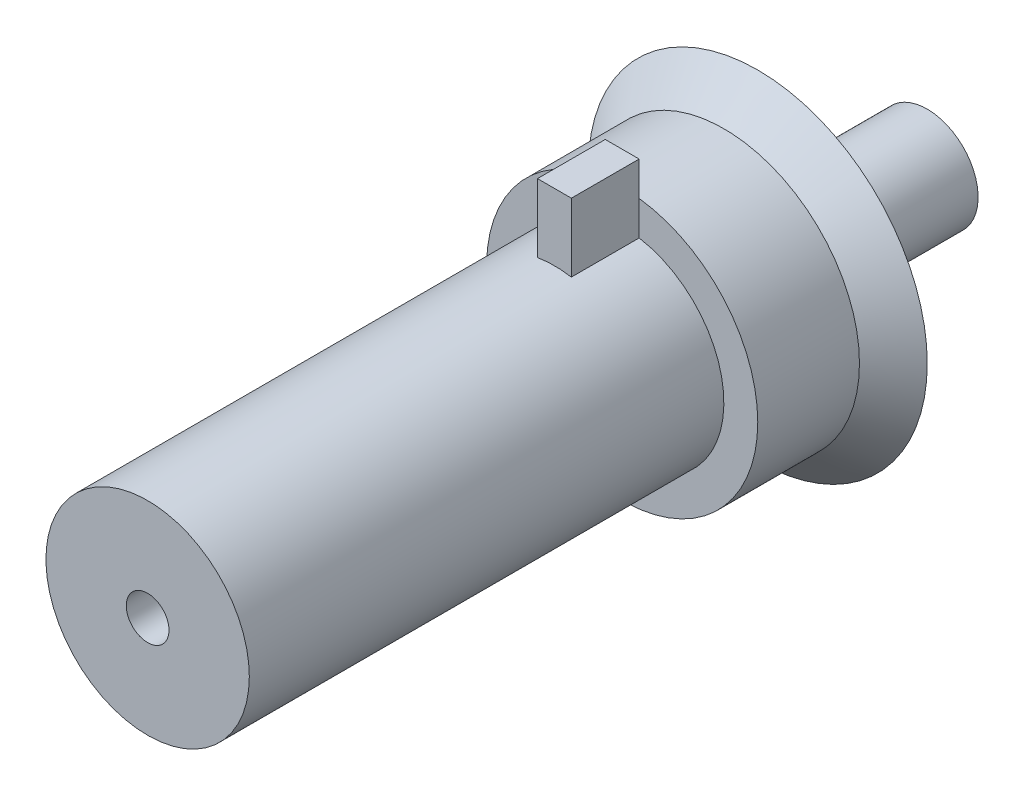
SolidWorks part; units mm, degrees
ref_plane "Front Plane" through (0, 0, 0) normal (0, 0, 1) x (1, 0, 0)
ref_plane "Top Plane" through (0, 0, 0) normal (0, 1, 0) x (1, 0, 0)
ref_plane "Right Plane" through (0, 0, 0) normal (1, 0, 0) x (0, 0, -1)
sketch "Sketch1" plane through (0, 0, 0) normal (0, 0, 1) x (1, 0, 0)
  circle A0 centre (0, 0) radius 15
  dimension "D1" = 30
extrude "Boss-Extrude1" add sketch "Sketch1" along normal blind 80
ref_plane "Plane1" through (0, 0, -10) normal (0, 0, -1) x (-1, 0, 0)
sketch "Sketch2" plane through (0, 0, -10) normal (0, 0, -1) x (-1, 0, 0)
  circle A0 centre (0, 0) radius 25
  dimension "D1" = 50
loft "Loft1" add profiles "Sketch1<2>", "Sketch2" connector at (1.8145, 14.8898, 0) connector at (2.7327, 24.8502, -10)
sketch "Sketch1<2>" plane through (0, 0, 0) normal (0, 0, 1) x (1, 0, 0) same geometry as "Sketch1"
sketch "Sketch3" plane through (0, 0, -10) normal (0, 0, -1) x (-1, 0, 0)
  circle A0 centre (0, 0) radius 7.5
  dimension "D1" = 15
extrude "Boss-Extrude2" add sketch "Sketch3" along normal blind 25
ref_plane "Plane2" through (0, 0, 10) normal (0, 0, 1) x (1, 0, 0)
sketch "Sketch4" plane through (0, 0, 10) normal (0, 0, 1) x (1, 0, 0)
  line L1 (-2.4968, -0.1256) -> (2.5032, -0.1256)
  line L2 (-2.4968, -0.1256) -> (-2.4968, 24.8744)
  line L3 (-2.4968, 24.8744) -> (2.5032, 24.8744)
  line L4 (2.5032, -0.1256) -> (2.5032, 24.8744)
  circle A0 centre (0, 0) radius 25 construction
  dimension "D1" = 2.5
  dimension "D2" = 5
  dimension "D3" = 25
extrude "Boss-Extrude3" add sketch "Sketch4" along normal blind 10
sketch "Sketch5" plane through (0, 0, 80) normal (0, 0, 1) x (1, 0, 0)
  circle A0 centre (0, 0) radius 3.15
  dimension "D1" = 6.3
extrude "Cut-Extrude1" cut sketch "Sketch5" against normal blind 6
sketch "Sketch6" plane through (0, 0, 10) normal (0, 0, 1) x (1, 0, 0)
  circle A0 centre (0, 0) radius 20
  dimension "D1" = 40
extrude "Boss-Extrude4" add sketch "Sketch6" against normal blind 15
